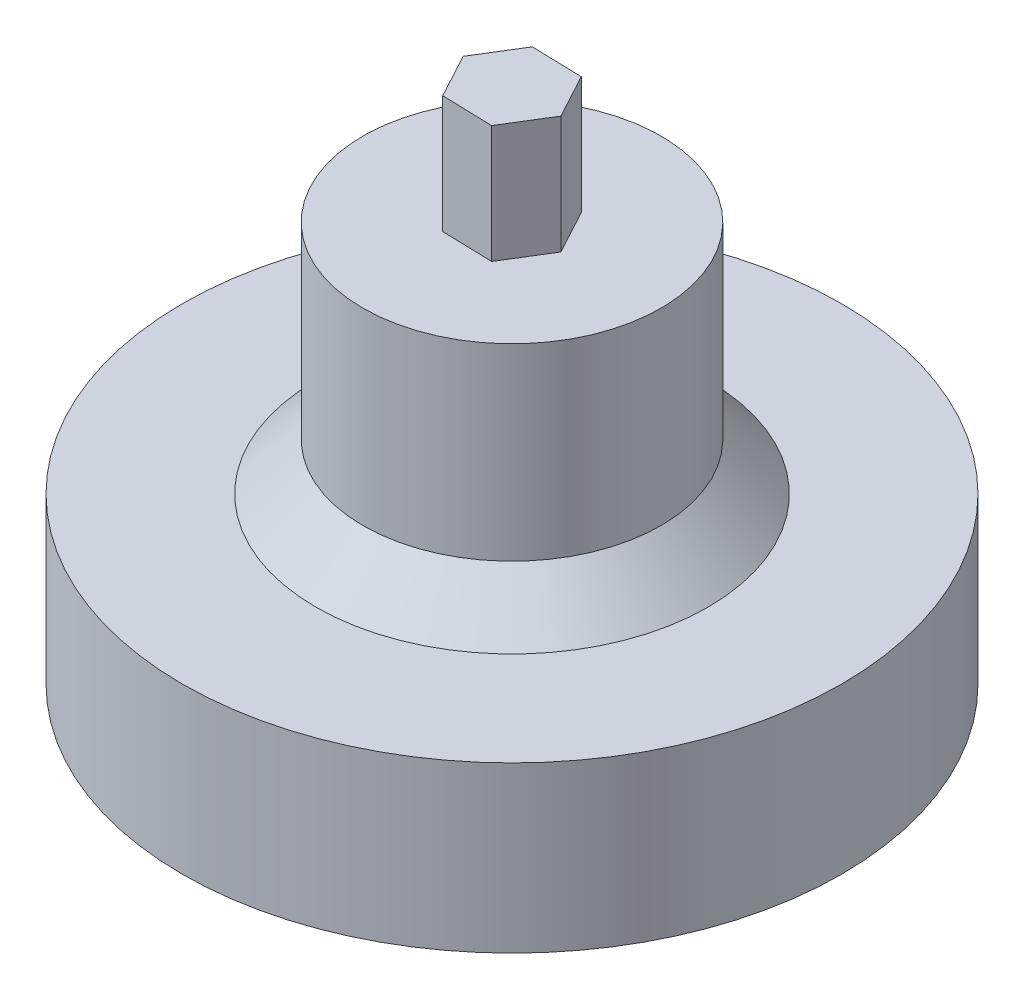
SolidWorks part; units mm, degrees
ref_plane "Front Plane" through (0, 0, 0) normal (0, 0, 1) x (1, 0, 0)
ref_plane "Top Plane" through (0, 0, 0) normal (0, 1, 0) x (1, 0, 0)
ref_plane "Right Plane" through (0, 0, 0) normal (1, 0, 0) x (0, 0, -1)
sketch "Sketch1" plane through (0, 0, 0) normal (0, 1, 0) x (1, 0, 0)
  circle A0 centre (0, 0) radius 35
  dimension "D1" = 70
extrude "Boss-Extrude1" add sketch "Sketch1" along normal blind 10
sketch "Sketch2" plane through (0, 0, 0) normal (0, -1, 0) x (1, 0, 0)
  line L0 (0, 0) -> (0, 29) construction
  line L1 (-2.5, 29) -> (2.5, 29)
  line L2 (-2.5, 29) -> (-4.8457, 34.6629)
  line L3 (2.5, 29) -> (4.8457, 34.6629)
  circle A0 centre (0, 0) radius 35 construction
  arc A1 (4.8457, 34.6629) -> (-4.8457, 34.6629) centre (0, 0) ccw
  dimension "D1" = 67.5
  dimension "D2" = 29
  dimension "D3" = 5
extrude "Boss-Extrude2" add sketch "Sketch2" along normal blind 11
fillet "Fillet1" radius 3 2 edges at (2.5, -5.5, 29) (-2.5, -5.5, 29)
pattern_circular "CirPattern1" count 16 over 360 about axis through (0, 0, 0) along (0, 1, 0) of "Boss-Extrude2", "Fillet1"
sketch "Sketch4" plane through (0, -11, 0) normal (0, -1, 0) x (1, 0, 0)
  circle A0 centre (0, 0) radius 35
  circle A1 centre (0, 0) radius 42
  arc A2 (4.8457, 34.6629) -> (-4.8457, 34.6629) centre (0, 0) ccw construction
  dimension "D1" = 7
extrude "Boss-Extrude3" add sketch "Sketch4" against normal up to surface (21 mm away) up to face at (0, 10, 35)
sketch "Sketch13" plane through (0, 0, 0) normal (0, -1, 0) x (1, 0, 0)
  line L48 (-14.8249, 27.2532) -> (-17.7417, 30.17)
  line L49 (-21.084, 27.9368) -> (-19.5054, 24.1258)
  line L50 (-20.1558, 20.8564) -> (-20.8564, 20.1558)
  line L51 (-24.1258, 19.5054) -> (-27.9368, 21.084)
  line L52 (-30.17, 17.7417) -> (-27.2532, 14.8249)
  line L53 (-26.6029, 11.5556) -> (-26.9821, 10.6401)
  line L54 (-29.7538, 8.7881) -> (-33.8787, 8.7881)
  line L55 (-34.6629, 4.8457) -> (-30.8519, 3.2671)
  line L56 (-29, 0.4955) -> (-29, -0.4955)
  line L57 (-30.8519, -3.2671) -> (-34.6629, -4.8457)
  line L58 (-33.8787, -8.7881) -> (-29.7538, -8.7881)
  line L59 (-26.9821, -10.6401) -> (-26.6029, -11.5556)
  line L60 (-27.2532, -14.8249) -> (-30.17, -17.7417)
  line L61 (-27.9368, -21.084) -> (-24.1258, -19.5054)
  line L62 (-20.8564, -20.1558) -> (-20.1558, -20.8564)
  line L63 (-19.5054, -24.1258) -> (-21.084, -27.9368)
  line L64 (-17.7417, -30.17) -> (-14.8249, -27.2532)
  line L65 (-11.5556, -26.6029) -> (-10.6401, -26.9821)
  line L66 (-8.7881, -29.7538) -> (-8.7881, -33.8787)
  line L67 (-4.8457, -34.6629) -> (-3.2671, -30.8519)
  line L68 (-0.4955, -29) -> (0.4955, -29)
  line L69 (3.2671, -30.8519) -> (4.8457, -34.6629)
  line L70 (8.7881, -33.8787) -> (8.7881, -29.7538)
  line L71 (10.6401, -26.9821) -> (11.5556, -26.6029)
  line L72 (14.8249, -27.2532) -> (17.7417, -30.17)
  line L73 (21.084, -27.9368) -> (19.5054, -24.1258)
  line L74 (20.1558, -20.8564) -> (20.8564, -20.1558)
  line L75 (24.1258, -19.5054) -> (27.9368, -21.084)
  line L76 (30.17, -17.7417) -> (27.2532, -14.8249)
  line L77 (26.6029, -11.5556) -> (26.9821, -10.6401)
  line L78 (29.7538, -8.7881) -> (33.8787, -8.7881)
  line L79 (34.6629, -4.8457) -> (30.8519, -3.2671)
  line L80 (29, -0.4955) -> (29, 0.4955)
  line L81 (30.8519, 3.2671) -> (34.6629, 4.8457)
  line L82 (33.8787, 8.7881) -> (29.7538, 8.7881)
  line L83 (26.9821, 10.6401) -> (26.6029, 11.5556)
  line L84 (27.2532, 14.8249) -> (30.17, 17.7417)
  line L85 (27.9368, 21.084) -> (24.1258, 19.5054)
  line L86 (20.8564, 20.1558) -> (20.1558, 20.8564)
  line L87 (19.5054, 24.1258) -> (21.084, 27.9368)
  line L88 (17.7417, 30.17) -> (14.8249, 27.2532)
  line L89 (11.5556, 26.6029) -> (10.6401, 26.9821)
  line L90 (8.7881, 29.7538) -> (8.7881, 33.8787)
  line L91 (4.8457, 34.6629) -> (3.2671, 30.8519)
  line L92 (0.4955, 29) -> (-0.4955, 29)
  line L93 (-3.2671, 30.8519) -> (-4.8457, 34.6629)
  line L94 (-8.7881, 33.8787) -> (-8.7881, 29.7538)
  line L95 (-10.6401, 26.9821) -> (-11.5556, 26.6029)
  line L96 (-14.8249, 27.2532) -> (-17.7417, 30.17)
  line L97 (-21.084, 27.9368) -> (-19.5054, 24.1258)
  line L98 (-20.1558, 20.8564) -> (-20.8564, 20.1558)
  line L99 (-24.1258, 19.5054) -> (-27.9368, 21.084)
  line L100 (-30.17, 17.7417) -> (-27.2532, 14.8249)
  line L101 (-26.6029, 11.5556) -> (-26.9821, 10.6401)
  line L102 (-29.7538, 8.7881) -> (-33.8787, 8.7881)
  line L103 (-34.6629, 4.8457) -> (-30.8519, 3.2671)
  line L104 (-29, 0.4955) -> (-29, -0.4955)
  line L105 (-30.8519, -3.2671) -> (-34.6629, -4.8457)
  line L106 (-33.8787, -8.7881) -> (-29.7538, -8.7881)
  line L107 (-26.9821, -10.6401) -> (-26.6029, -11.5556)
  line L108 (-27.2532, -14.8249) -> (-30.17, -17.7417)
  line L109 (-27.9368, -21.084) -> (-24.1258, -19.5054)
  line L110 (-20.8564, -20.1558) -> (-20.1558, -20.8564)
  line L111 (-19.5054, -24.1258) -> (-21.084, -27.9368)
  line L112 (-17.7417, -30.17) -> (-14.8249, -27.2532)
  line L113 (-11.5556, -26.6029) -> (-10.6401, -26.9821)
  line L114 (-8.7881, -29.7538) -> (-8.7881, -33.8787)
  line L115 (-4.8457, -34.6629) -> (-3.2671, -30.8519)
  line L116 (-0.4955, -29) -> (0.4955, -29)
  line L117 (3.2671, -30.8519) -> (4.8457, -34.6629)
  line L118 (8.7881, -33.8787) -> (8.7881, -29.7538)
  line L119 (10.6401, -26.9821) -> (11.5556, -26.6029)
  line L120 (14.8249, -27.2532) -> (17.7417, -30.17)
  line L121 (21.084, -27.9368) -> (19.5054, -24.1258)
  line L122 (20.1558, -20.8564) -> (20.8564, -20.1558)
  line L123 (24.1258, -19.5054) -> (27.9368, -21.084)
  line L124 (30.17, -17.7417) -> (27.2532, -14.8249)
  line L125 (26.6029, -11.5556) -> (26.9821, -10.6401)
  line L126 (29.7538, -8.7881) -> (33.8787, -8.7881)
  line L127 (34.6629, -4.8457) -> (30.8519, -3.2671)
  line L128 (29, -0.4955) -> (29, 0.4955)
  line L129 (30.8519, 3.2671) -> (34.6629, 4.8457)
  line L130 (33.8787, 8.7881) -> (29.7538, 8.7881)
  line L131 (26.9821, 10.6401) -> (26.6029, 11.5556)
  line L132 (27.2532, 14.8249) -> (30.17, 17.7417)
  line L133 (27.9368, 21.084) -> (24.1258, 19.5054)
  line L134 (20.8564, 20.1558) -> (20.1558, 20.8564)
  line L135 (19.5054, 24.1258) -> (21.084, 27.9368)
  line L136 (17.7417, 30.17) -> (14.8249, 27.2532)
  line L137 (11.5556, 26.6029) -> (10.6401, 26.9821)
  line L138 (8.7881, 29.7538) -> (8.7881, 33.8787)
  line L139 (4.8457, 34.6629) -> (3.2671, 30.8519)
  line L140 (0.4955, 29) -> (-0.4955, 29)
  line L141 (-3.2671, 30.8519) -> (-4.8457, 34.6629)
  line L142 (-8.7881, 33.8787) -> (-8.7881, 29.7538)
  line L143 (-10.6401, 26.9821) -> (-11.5556, 26.6029)
  circle A0 centre (0, 0) radius 28
  arc A48 (-17.7417, 30.17) -> (-21.084, 27.9368) centre (0, 0) ccw
  arc A49 (-20.1558, 20.8564) -> (-19.5054, 24.1258) centre (-22.2771, 22.9778) ccw
  arc A50 (-24.1258, 19.5054) -> (-20.8564, 20.1558) centre (-22.9778, 22.2771) ccw
  arc A51 (-27.9368, 21.084) -> (-30.17, 17.7417) centre (0, 0) ccw
  arc A52 (-26.6029, 11.5556) -> (-27.2532, 14.8249) centre (-29.3745, 12.7036) ccw
  arc A53 (-29.7538, 8.7881) -> (-26.9821, 10.6401) centre (-29.7538, 11.7881) ccw
  arc A54 (-33.8787, 8.7881) -> (-34.6629, 4.8457) centre (0, 0) ccw
  arc A55 (-29, 0.4955) -> (-30.8519, 3.2671) centre (-32, 0.4955) ccw
  arc A56 (-30.8519, -3.2671) -> (-29, -0.4955) centre (-32, -0.4955) ccw
  arc A57 (-34.6629, -4.8457) -> (-33.8787, -8.7881) centre (0, 0) ccw
  arc A58 (-26.9821, -10.6401) -> (-29.7538, -8.7881) centre (-29.7538, -11.7881) ccw
  arc A59 (-27.2532, -14.8249) -> (-26.6029, -11.5556) centre (-29.3745, -12.7036) ccw
  arc A60 (-30.17, -17.7417) -> (-27.9368, -21.084) centre (0, 0) ccw
  arc A61 (-20.8564, -20.1558) -> (-24.1258, -19.5054) centre (-22.9778, -22.2771) ccw
  arc A62 (-19.5054, -24.1258) -> (-20.1558, -20.8564) centre (-22.2771, -22.9778) ccw
  arc A63 (-21.084, -27.9368) -> (-17.7417, -30.17) centre (0, 0) ccw
  arc A64 (-11.5556, -26.6029) -> (-14.8249, -27.2532) centre (-12.7036, -29.3745) ccw
  arc A65 (-8.7881, -29.7538) -> (-10.6401, -26.9821) centre (-11.7881, -29.7538) ccw
  arc A66 (-8.7881, -33.8787) -> (-4.8457, -34.6629) centre (0, 0) ccw
  arc A67 (-0.4955, -29) -> (-3.2671, -30.8519) centre (-0.4955, -32) ccw
  arc A68 (3.2671, -30.8519) -> (0.4955, -29) centre (0.4955, -32) ccw
  arc A69 (4.8457, -34.6629) -> (8.7881, -33.8787) centre (0, 0) ccw
  arc A70 (10.6401, -26.9821) -> (8.7881, -29.7538) centre (11.7881, -29.7538) ccw
  arc A71 (14.8249, -27.2532) -> (11.5556, -26.6029) centre (12.7036, -29.3745) ccw
  arc A72 (17.7417, -30.17) -> (21.084, -27.9368) centre (0, 0) ccw
  arc A73 (20.1558, -20.8564) -> (19.5054, -24.1258) centre (22.2771, -22.9778) ccw
  arc A74 (24.1258, -19.5054) -> (20.8564, -20.1558) centre (22.9778, -22.2771) ccw
  arc A75 (27.9368, -21.084) -> (30.17, -17.7417) centre (0, 0) ccw
  arc A76 (26.6029, -11.5556) -> (27.2532, -14.8249) centre (29.3745, -12.7036) ccw
  arc A77 (29.7538, -8.7881) -> (26.9821, -10.6401) centre (29.7538, -11.7881) ccw
  arc A78 (33.8787, -8.7881) -> (34.6629, -4.8457) centre (0, 0) ccw
  arc A79 (29, -0.4955) -> (30.8519, -3.2671) centre (32, -0.4955) ccw
  arc A80 (30.8519, 3.2671) -> (29, 0.4955) centre (32, 0.4955) ccw
  arc A81 (34.6629, 4.8457) -> (33.8787, 8.7881) centre (0, 0) ccw
  arc A82 (26.9821, 10.6401) -> (29.7538, 8.7881) centre (29.7538, 11.7881) ccw
  arc A83 (27.2532, 14.8249) -> (26.6029, 11.5556) centre (29.3745, 12.7036) ccw
  arc A84 (30.17, 17.7417) -> (27.9368, 21.084) centre (0, 0) ccw
  arc A85 (20.8564, 20.1558) -> (24.1258, 19.5054) centre (22.9778, 22.2771) ccw
  arc A86 (19.5054, 24.1258) -> (20.1558, 20.8564) centre (22.2771, 22.9778) ccw
  arc A87 (21.084, 27.9368) -> (17.7417, 30.17) centre (0, 0) ccw
  arc A88 (11.5556, 26.6029) -> (14.8249, 27.2532) centre (12.7036, 29.3745) ccw
  arc A89 (8.7881, 29.7538) -> (10.6401, 26.9821) centre (11.7881, 29.7538) ccw
  arc A90 (8.7881, 33.8787) -> (4.8457, 34.6629) centre (0, 0) ccw
  arc A91 (0.4955, 29) -> (3.2671, 30.8519) centre (0.4955, 32) ccw
  arc A92 (-3.2671, 30.8519) -> (-0.4955, 29) centre (-0.4955, 32) ccw
  arc A93 (-4.8457, 34.6629) -> (-8.7881, 33.8787) centre (0, 0) ccw
  arc A94 (-10.6401, 26.9821) -> (-8.7881, 29.7538) centre (-11.7881, 29.7538) ccw
  arc A95 (-14.8249, 27.2532) -> (-11.5556, 26.6029) centre (-12.7036, 29.3745) ccw
  arc A96 (-17.7417, 30.17) -> (-21.084, 27.9368) centre (0, 0) ccw
  arc A97 (-20.1558, 20.8564) -> (-19.5054, 24.1258) centre (-22.2771, 22.9778) ccw
  arc A98 (-24.1258, 19.5054) -> (-20.8564, 20.1558) centre (-22.9778, 22.2771) ccw
  arc A99 (-27.9368, 21.084) -> (-30.17, 17.7417) centre (0, 0) ccw
  arc A100 (-26.6029, 11.5556) -> (-27.2532, 14.8249) centre (-29.3745, 12.7036) ccw
  arc A101 (-29.7538, 8.7881) -> (-26.9821, 10.6401) centre (-29.7538, 11.7881) ccw
  arc A102 (-33.8787, 8.7881) -> (-34.6629, 4.8457) centre (0, 0) ccw
  arc A103 (-29, 0.4955) -> (-30.8519, 3.2671) centre (-32, 0.4955) ccw
  arc A104 (-30.8519, -3.2671) -> (-29, -0.4955) centre (-32, -0.4955) ccw
  arc A105 (-34.6629, -4.8457) -> (-33.8787, -8.7881) centre (0, 0) ccw
  arc A106 (-26.9821, -10.6401) -> (-29.7538, -8.7881) centre (-29.7538, -11.7881) ccw
  arc A107 (-27.2532, -14.8249) -> (-26.6029, -11.5556) centre (-29.3745, -12.7036) ccw
  arc A108 (-30.17, -17.7417) -> (-27.9368, -21.084) centre (0, 0) ccw
  arc A109 (-20.8564, -20.1558) -> (-24.1258, -19.5054) centre (-22.9778, -22.2771) ccw
  arc A110 (-19.5054, -24.1258) -> (-20.1558, -20.8564) centre (-22.2771, -22.9778) ccw
  arc A111 (-21.084, -27.9368) -> (-17.7417, -30.17) centre (0, 0) ccw
  arc A112 (-11.5556, -26.6029) -> (-14.8249, -27.2532) centre (-12.7036, -29.3745) ccw
  arc A113 (-8.7881, -29.7538) -> (-10.6401, -26.9821) centre (-11.7881, -29.7538) ccw
  arc A114 (-8.7881, -33.8787) -> (-4.8457, -34.6629) centre (0, 0) ccw
  arc A115 (-0.4955, -29) -> (-3.2671, -30.8519) centre (-0.4955, -32) ccw
  arc A116 (3.2671, -30.8519) -> (0.4955, -29) centre (0.4955, -32) ccw
  arc A117 (4.8457, -34.6629) -> (8.7881, -33.8787) centre (0, 0) ccw
  arc A118 (10.6401, -26.9821) -> (8.7881, -29.7538) centre (11.7881, -29.7538) ccw
  arc A119 (14.8249, -27.2532) -> (11.5556, -26.6029) centre (12.7036, -29.3745) ccw
  arc A120 (17.7417, -30.17) -> (21.084, -27.9368) centre (0, 0) ccw
  arc A121 (20.1558, -20.8564) -> (19.5054, -24.1258) centre (22.2771, -22.9778) ccw
  arc A122 (24.1258, -19.5054) -> (20.8564, -20.1558) centre (22.9778, -22.2771) ccw
  arc A123 (27.9368, -21.084) -> (30.17, -17.7417) centre (0, 0) ccw
  arc A124 (26.6029, -11.5556) -> (27.2532, -14.8249) centre (29.3745, -12.7036) ccw
  arc A125 (29.7538, -8.7881) -> (26.9821, -10.6401) centre (29.7538, -11.7881) ccw
  arc A126 (33.8787, -8.7881) -> (34.6629, -4.8457) centre (0, 0) ccw
  arc A127 (29, -0.4955) -> (30.8519, -3.2671) centre (32, -0.4955) ccw
  arc A128 (30.8519, 3.2671) -> (29, 0.4955) centre (32, 0.4955) ccw
  arc A129 (34.6629, 4.8457) -> (33.8787, 8.7881) centre (0, 0) ccw
  arc A130 (26.9821, 10.6401) -> (29.7538, 8.7881) centre (29.7538, 11.7881) ccw
  arc A131 (27.2532, 14.8249) -> (26.6029, 11.5556) centre (29.3745, 12.7036) ccw
  arc A132 (30.17, 17.7417) -> (27.9368, 21.084) centre (0, 0) ccw
  arc A133 (20.8564, 20.1558) -> (24.1258, 19.5054) centre (22.9778, 22.2771) ccw
  arc A134 (19.5054, 24.1258) -> (20.1558, 20.8564) centre (22.2771, 22.9778) ccw
  arc A135 (21.084, 27.9368) -> (17.7417, 30.17) centre (0, 0) ccw
  arc A136 (11.5556, 26.6029) -> (14.8249, 27.2532) centre (12.7036, 29.3745) ccw
  arc A137 (8.7881, 29.7538) -> (10.6401, 26.9821) centre (11.7881, 29.7538) ccw
  arc A138 (8.7881, 33.8787) -> (4.8457, 34.6629) centre (0, 0) ccw
  arc A139 (0.4955, 29) -> (3.2671, 30.8519) centre (0.4955, 32) ccw
  arc A140 (-3.2671, 30.8519) -> (-0.4955, 29) centre (-0.4955, 32) ccw
  arc A141 (-4.8457, 34.6629) -> (-8.7881, 33.8787) centre (0, 0) ccw
  arc A142 (-10.6401, 26.9821) -> (-8.7881, 29.7538) centre (-11.7881, 29.7538) ccw
  arc A143 (-14.8249, 27.2532) -> (-11.5556, 26.6029) centre (-12.7036, 29.3745) ccw
  dimension "D2" = 56
  dimension "D1" = 0
extrude "Boss-Extrude10" add sketch "Sketch13" along normal blind 6
sketch "Sketch5" plane through (0, 10, 0) normal (0, 1, 0) x (1, 0, 0)
  circle A0 centre (0, 0) radius 19
  dimension "D1" = 38
extrude "Boss-Extrude4" add sketch "Sketch5" along normal blind 30
sketch "Sketch6" plane through (0, 0, 0) normal (0, -1, 0) x (1, 0, 0)
  circle A0 centre (0, 0) radius 10
  dimension "D1" = 20
extrude "Cut-Extrude1" cut sketch "Sketch6" against normal blind 25
chamfer "Chamfer2" distance 6 angle 45 2 edges at (0, 10, 19) (0, 25, -10)
sketch "Sketch14" plane through (0, 40, 0) normal (0, 1, 0) x (1, 0, 0)
  line L1 (3.3671, 5.4613) -> (-3.046, 5.6466)
  line L2 (-3.046, 5.6466) -> (-6.4131, 0.1854)
  line L3 (-6.4131, 0.1854) -> (-3.3671, -5.4613)
  line L4 (-3.3671, -5.4613) -> (3.046, -5.6466)
  line L5 (3.046, -5.6466) -> (6.4131, -0.1854)
  line L6 (6.4131, -0.1854) -> (3.3671, 5.4613)
  circle A0 centre (0, 0) radius 5.5562 construction
  dimension "D1" = 11.1125
extrude "Boss-Extrude11" add sketch "Sketch14" along normal blind 15
